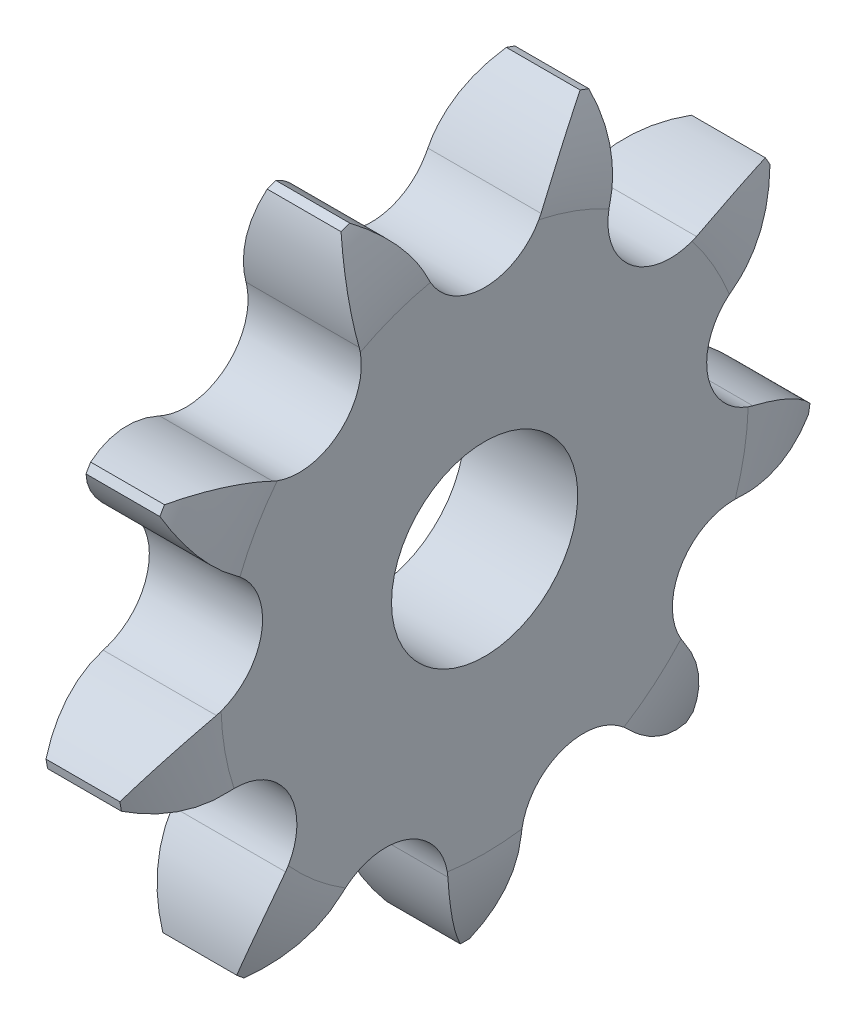
SolidWorks part; units mm, degrees
ref_plane "Plane1" through (0, 0, 0) normal (0, 0, 1) x (1, 0, 0)
ref_plane "Plane2" through (0, 0, 0) normal (0, 1, 0) x (1, 0, 0)
ref_plane "Plane3" through (0, 0, 0) normal (1, 0, 0) x (0, 0, -1)
sketch "Clipboard" plane through (0, 0, 0) normal (0, 1, 0) x (1, 0, 0)
  line L0 (0, 0) -> (12.5436, -1.9867)
  line L1 (-15, 0) -> (100, 0) construction
  line L2 (0, 0) -> (-0.8416, 0.9512)
  line L3 (0, 0) -> (-11.863, 4.5341)
  line L4 (0, 0) -> (3.0618, 0.4849)
  line L5 (0, 0) -> (-2.8109, -1.0484)
  line L6 (0, 0) -> (-6.0514, -4.0829)
  line L7 (-0.8416, 0.9512) -> (8.5146, 2.6009)
  line L8 (-76.2, 38.1) -> (-75.2, 38.1)
  line L9 (-73.4321, 41.7084) -> (-72.837, 41.7846)
  line L10 (-73.4741, 12.9512) -> (-59.0941, 12.9512)
  circle A0 centre (0, 0) radius 3.975
  circle A1 centre (0, 0) radius 10.0465
  circle A2 centre (0, 0) radius 25
  dimension "Num_teeth" = 9
  dimension "Thickness" = 7.3
sketch "BasProSke" plane through (0, 0, 0) normal (0, 1, 0) x (1, 0, 0)
  line L0 (-10, 0) -> (60, 0) construction
  line L1 (0, 0) -> (0, 16.9929)
  line L2 (0, 0) -> (7.3, 0)
  line L3 (7.3, 0) -> (7.3, 16.9929)
  line L4 (6.03, 22.5287) -> (1.27, 22.5287)
  arc A0 (0, 16.9929) -> (1.27, 22.5287) centre (12.7, 16.9929) cw
  arc A1 (7.3, 16.9929) -> (6.03, 22.5287) centre (-5.4, 16.9929) ccw
  dimension "D1" = 12.7
  dimension "Thickness" = 7.3
  dimension "Diameter" = 45.0573
revolve "Base-Revolve" add sketch "BasProSke" angle 360 about L0
sketch "TooCutSke" plane through (0, 0, 0) normal (1, 0, 0) x (0, 0, -1)
  line L0 (0, 18.6059) -> (3.6386, 16.9092) construction
  line L1 (0, 0) -> (0, 107) construction
  line L2 (0, 18.6059) -> (-10, 18.6059) construction
  line L3 (0, 18.6059) -> (-3.6386, 16.9092) construction
  arc A0 (3.6386, 16.9092) -> (7.9748, 21.6037) centre (13.1494, 12.4742) cw
  arc A1 (3.6386, 16.9092) -> (-3.6386, 16.9092) centre (0, 18.6059) cw
  arc A2 (-3.6386, 16.9092) -> (-7.9748, 21.6037) centre (-13.1494, 12.4742) ccw
  arc A3 (7.9748, 21.6037) -> (-7.9748, 21.6037) centre (0, 0) ccw
extrude "ToothCut" cut sketch "TooCutSke" along normal through all
pattern_circular "TeethCuts" count 9 every 40 about axis through (-10, 0, 0) along (1, 0, 0) of "ToothCut"
sketch "HubNeaOneSke" plane through (0, 0, 0) normal (-1, 0, 0) x (0, 0, 1)
  circle A0 centre (0, 0) radius 10.0465
  dimension "Diameter" = 20.093
extrude "HubNearOne" [suppressed] add sketch "HubNeaOneSke" along normal blind 2.2005
fillet "HubNearOneFillet" [suppressed] radius 0.6
sketch "HubNeaBotSke" plane through (0, 0, 0) normal (-1, 0, 0) x (0, 0, 1)
  circle A0 centre (0, 0) radius 10.0465
  dimension "Diameter" = 20.093
extrude "HubNearBoth" [suppressed] add sketch "HubNeaBotSke" along normal blind 1.1003
fillet "HubNearBothFillet" [suppressed] radius 0.6
ref_plane "FarPln" through (7.3, 0, 0) normal (1, 0, 0) x (0, 0, -1)
sketch "HubFarSke" plane through (7.3, 0, 0) normal (1, 0, 0) x (0, 0, -1)
  circle A0 centre (0, 0) radius 10.0465
  dimension "Diameter" = 20.093
extrude "HubFar" [suppressed] add sketch "HubFarSke" along normal blind 1.1003
fillet "HubFarFillet" [suppressed] radius 0.6
sketch "BorSke" plane through (0, 0, 0) normal (1, 0, 0) x (0, 0, -1)
  circle A0 centre (0, 0) radius 6
  dimension "Diameter" = 12
extrude "Bore" cut sketch "BorSke" along normal mid plane 19.001
sketch "KeySke" plane through (0, 0, 0) normal (1, 0, 0) x (0, 0, -1)
  line L0 (-1, 0) -> (-1, 7)
  line L1 (-1, 7) -> (1, 7)
  line L2 (1, 7) -> (1, 0)
  line L3 (0, 0) -> (0, 34) construction
  line L4 (-1, 0) -> (1, 0)
  dimension "Width" = 2
extrude "Keyway" [suppressed] cut sketch "KeySke" along normal mid plane 19.001
pattern_circular "Keyway2" [suppressed] count 2 every 90 about axis through (-10, 0, 0) along (1, 0, 0) reverse direction yes
equation "' \"Pitch@Clipboard\" = 12.7"
equation "' \"Num_strands@Clipboard\" = 1"
equation "' \"Num_teeth@Clipboard\" = 9"
equation "' \"Hub_dia@Clipboard\" = 50"
equation "' \"Overall_len@Clipboard\" = 3"
equation "' \"Diameter@BorSke\" = 12"
equation "' \"T_dim@Clipboard\" = 1"
equation "' \"Width@KeySke\" = 2"
equation "' \"Dr@Clipboard\" = 7.95"
equation "' \"Face_width@Clipboard\" = 7.3"
equation "' \"Side_radius@Clipboard\" = 12.7"
equation "' \"Side_relief@Clipboard\" = 1.27"
equation "' \"Transv_pitch@Clipboard\" = 14.38"
equation "' \"Show_teeth@Clipboard\" = 9"
equation "' \"Fillet_rad@Clipboard\" = 0.6"
equation "' \"Plate_wid@Clipboard\" = 12"
equation "\"Num_teeth@Clipboard\" = int( \"Num_teeth@Clipboard\" )"
equation "\"Num_teeth@Clipboard\" = ((sgn( \"Num_teeth@Clipboard\" - 5.0)+1)*( \"Num_teeth@Clipboard\" - 5.0))/2 +5.0"
equation "\"Num_teeth@Clipboard\" = ((sgn( \"Num_teeth@Clipboard\" - 200.0)-1)*( \"Num_teeth@Clipboard\" - 200.0))/-2 +200.0"
equation "\"MHD@Clipboard\" = \"Pitch@Clipboard\" * (1.0 / tan(3.14159265 / \"Num_teeth@Clipboard\" )) - 1.05 * \"Plate_wid@Clipboard\" - 2.0 * \"Fillet_rad@Clipboard\" - 1.0"
equation "\"Thickness@Clipboard\"  = \"Face_width@Clipboard\" + (\"Num_strands@Clipboard\" - 1) * \"Transv_pitch@Clipboard\""
equation "\"OAL@Clipboard\" = \"Thickness@Clipboard\" + 2 * \"Fillet_rad@Clipboard\" + 1"
equation "\"MHD@Clipboard\" = ((sgn( \"MHD@Clipboard\" - \"Hub_dia@Clipboard\" )-1)*( \"MHD@Clipboard\" - \"Hub_dia@Clipboard\" ))/-2+ \"Hub_dia@Clipboard\""
equation "\"OAL@Clipboard\" = ((sgn( \"OAL@Clipboard\" - \"Overall_len@Clipboard\" )+1)*( \"OAL@Clipboard\" - \"Overall_len@Clipboard\" ))/2 + \"Overall_len@Clipboard\" + 0.0005"
equation "\"Num_teeth@TeethCuts\" = int( \"Show_teeth@Clipboard\" ) + 1"
equation "\"Num_teeth@TeethCuts\" = ((sgn( \"Num_teeth@TeethCuts\" - \"Num_teeth@Clipboard\" )-1)*( \"Num_teeth@TeethCuts\" - \"Num_teeth@Clipboard\" ))/-2+ \"Num_teeth@Clipboard\""
equation "\"Num_teeth@TeethCuts\" = ((sgn( \"Num_teeth@TeethCuts\" - 2.0)+1)*( \"Num_teeth@TeethCuts\" - 2.0))/2 +2.0"
equation "\"Angle@TeethCuts\" = 360.0 / \"Num_teeth@Clipboard\""
equation "\"Seat_radius@TooCutSke\" = ( \"Pitch@Clipboard\" / 2.0) / sin(3.14159265 / \"Num_teeth@Clipboard\" ) - \"Dr@Clipboard\" / 2.0 + \"Dr@Clipboard\" * 0.505"
equation "\"R1@TooCutSke\"  = \"Dr@Clipboard\" * 0.505"
equation "\"X@TooCutSke\" = 140.0 - (90.0 / \"Num_teeth@Clipboard\")"
equation "\"R2@TooCutSke\" = 0.12 * \"Dr@Clipboard\" * ( \"Num_teeth@Clipboard\" + 2.0)"
equation "\"Overcut@TooCutSke\" = 0.5 + 0.625 * \"Pitch@Clipboard\" - 0.5 * \"Dr@Clipboard\"  +  \"Pitch@Clipboard\" / 2.0 / sin(3.14159265 / \"Num_teeth@Clipboard\" )"
equation "\"Diameter@BasProSke\" = 2.0 * ( 0.625 * \"Pitch@Clipboard\" - 0.5 * \"Dr@Clipboard\"  +  \"Pitch@Clipboard\" / 2.0 / sin(3.14159265 / \"Num_teeth@Clipboard\" ))"
equation "\"Thickness@BasProSke\"  = \"Thickness@Clipboard\""
equation "\"G1@BasProSke\" =  \"Side_relief@Clipboard\""
equation "\"G2@BasProSke\" =  \"Side_relief@Clipboard\""
equation "\"D1@BasProSke\" =  \"Side_radius@Clipboard\""
equation "\"Diameter@HubNeaOneSke\" = \"MHD@Clipboard\""
equation "\"Length@HubNearOne\" = \"OAL@Clipboard\" - \"Thickness@BasProSke\""
equation "\"Diameter@HubNeaBotSke\" = \"MHD@Clipboard\""
equation "\"Length@HubNearBoth\" = ( \"OAL@Clipboard\" - \"Thickness@BasProSke\" ) / 2.0"
equation "\"D1@HubNearOneFillet\" = \"Fillet_rad@Clipboard\""
equation "\"D1@HubNearBothFillet\" = \"Fillet_rad@Clipboard\""
equation "\"Thickness@FarPln\" = \"Thickness@BasProSke\""
equation "\"Diameter@HubFarSke\" = \"MHD@Clipboard\""
equation "\"Length@HubFar\" = ( \"OAL@Clipboard\" - \"Thickness@BasProSke\" ) / 2.0"
equation "\"D1@HubFarFillet\" = \"Fillet_rad@Clipboard\""
equation "\"D1@Bore\" = \"OAL@Clipboard\" * 2.0"
equation "\"D1@Keyway\" = \"OAL@Clipboard\" * 2.0"
equation "\"Offset@KeySke\" = \"T_dim@Clipboard\" + \"Diameter@BorSke\" / 2.0"
